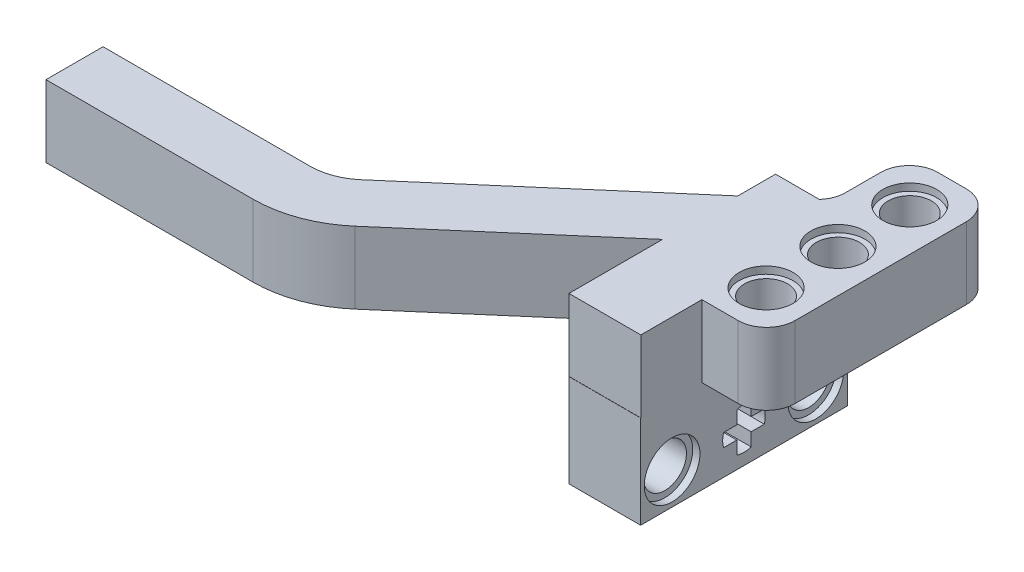
SolidWorks part; units mm, degrees
ref_plane "Front Plane" through (0, 0, 0) normal (0, 0, 1) x (1, 0, 0)
ref_plane "Top Plane" through (0, 0, 0) normal (0, 1, 0) x (1, 0, 0)
ref_plane "Right Plane" through (0, 0, 0) normal (1, 0, 0) x (0, 0, -1)
sketch "Sketch6" plane through (0, 0, 0) normal (0, 1, 0) x (1, 0, 0)
  line L1 (-4.7625, 12.7) -> (4.7625, 12.7)
  line L2 (-4.7625, 12.7) -> (-4.7625, -12.7)
  line L3 (-4.7625, -12.7) -> (4.7625, -12.7)
  line L4 (4.7625, 12.7) -> (4.7625, -12.7)
  line L5 (-4.7625, 12.7) -> (4.7625, -12.7) construction
  line L6 (-4.7625, -12.7) -> (4.7625, 12.7) construction
  point P0 (0, 0)
  dimension "D1" = 9.525
  dimension "D2" = 25.4
extrude "Boss-Extrude1" add sketch "Sketch6" against normal blind 8
sketch "Sketch16" plane through (0, 0, 0) normal (0, -1, 0) x (1, 0, 0)
  line L1 (-2.4423, -3.5) -> (-10.4423, -3.5)
  line L2 (-2.4423, -3.5) -> (-2.4423, 19.5)
  line L3 (-2.4423, 19.5) -> (-10.4423, 19.5)
  line L4 (-10.4423, -3.5) -> (-10.4423, 19.5)
  line L5 (-2.4423, -3.5) -> (-10.4423, 19.5) construction
  line L6 (-2.4423, 19.5) -> (-10.4423, -3.5) construction
  line L7 (-4.7625, -12.7) -> (-4.7625, 12.7) construction
  point P0 (-6.4423, 8)
  point P5 (6.4422, 5.5566)
  point P7 (-6.5033, 8.0602)
  point P10 (3.2311, 3.8232)
  point P12 (-4.7625, 0)
  dimension "D1" = 6.4423
  dimension "D2" = 8
  dimension "D3" = 8
  dimension "D4" = 23
extrude "Boss-Extrude6" add sketch "Sketch16" along normal up to surface (8 mm away) up to face at (0, -8, 0)
sketch "Sketch7" plane through (0, 0, 0) normal (0, 1, 0) x (1, 0, 0)
  circle A0 centre (0, 8) radius 2.4
  circle A1 centre (0, 0) radius 2.4
  circle A2 centre (0, -8) radius 2.4
  circle A3 centre (0, 8) radius 3
  circle A4 centre (0, 0) radius 3
  circle A5 centre (0, -8) radius 3
  dimension "D3" = 4.8
  dimension "D1" = 8
  dimension "D2" = 8
  dimension "D4" = 0.6
extrude "Cut-Extrude1" cut sketch "Sketch7" against normal blind 0.8
extrude "Cut-Extrude2" cut sketch "Sketch7<3>" against normal blind 7.2 contours A0 | A1 | A2 region at (0, 0, -8) region at (0, 0, 0) region at (0, 0, 8)
sketch "Sketch7<3>" plane through (0, 0, 0) normal (0, 1, 0) x (1, 0, 0) same geometry as "Sketch7"
sketch "Sketch9" plane through (0, -7.2, -7.2) normal (0, 1, 0) x (1, 0, 0)
  circle A0 centre (0, 0.8) radius 2.4
  circle A1 centre (0, -7.2) radius 2.4
  circle A2 centre (0, -15.2) radius 2.4
  circle A3 centre (0, 0.8) radius 3
  circle A4 centre (0, -7.2) radius 3
  circle A5 centre (0, -15.2) radius 3
  dimension "D3" = 4.8
  dimension "D1" = 8
  dimension "D2" = 8
  dimension "D4" = 0.6
extrude "Cut-Extrude4" cut sketch "Sketch9" against normal blind 0.8 contours A3 | A4 | A5
ref_plane "Plane4" through (0, 0, 28) normal (0, 0, 1) x (1, 0, 0)
sketch "Sketch10" plane through (0, -8, 0) normal (0, -1, 0) x (-1, 0, 0)
  line L1 (4.7625, 4.1904) -> (34.7625, -21.65)
  line L2 (4.7625, 4.1904) -> (4.7625, -4.1904) construction
  line L3 (34.7625, -21.65) -> (60.1625, -21.65)
  line L4 (60.1625, -21.65) -> (60.1625, -28)
  line L5 (-57.9984, -28) -> (57.9984, -28) construction
  line L8 (4.7625, -4.1904) -> (32.4047, -28)
  line L10 (4.7625, 4.1904) -> (4.7625, -4.1904)
  line L14 (4.7625, 12.7) -> (4.7625, 3.5) construction
  line L18 (32.4047, -28) -> (60.1625, -28)
  point P2 (4.7625, 0)
  dimension "D1" = 30
  dimension "D2" = 6.35
  dimension "D3" = 25.4
  dimension "D4" = 6.35
extrude "Boss-Extrude3" add sketch "Sketch10" against normal up to surface (8 mm away) up to face at (0, 0, -5)
fillet "Fillet1" radius 3.175 1 edges at (-4.7625, -4, -4.1904)
fillet "Fillet3" radius 3.175 3 edges at (4.7625, -4, -12.7) (4.7625, -4, 12.7) (-4.7625, -4, -12.7)
fillet "Fillet6" radius 12.7 1 edges at (-32.4047, -4, 28)
fillet "Fillet7" radius 6.35 1 edges at (-34.7625, -4, 21.65)
sketch "Sketch11" plane through (0, -8, 0) normal (0, -1, 0) x (-1, 0, 0)
  line L0 (4.7625, 9.525) -> (4.7625, 5.6089) construction
  line L1 (10.4422, -19.5186) -> (2.4422, -19.5186)
  line L2 (10.4422, -19.5186) -> (10.4422, 3.4814)
  line L3 (10.4422, 3.4814) -> (2.4422, 3.4814)
  line L4 (2.4422, -19.5186) -> (2.4422, 3.4814)
  line L5 (10.4422, -19.5186) -> (2.4422, 3.4814) construction
  line L6 (10.4422, 3.4814) -> (2.4422, -19.5186) construction
  point P0 (6.4422, -8.0186)
  point P5 (6.4422, 5.5566)
  point P9 (4.7625, 7.5669)
  point P10 (3.2311, 3.8232)
  dimension "D1" = 6.4422
  dimension "D2" = 15.5855
  dimension "D3" = 8
  dimension "D4" = 23
extrude "Boss-Extrude4" add sketch "Sketch11" along normal blind 6.7462 contours L4 L3 L2 L1
sketch "Sketch13" plane through (-2.4423, 0, 0) normal (1, 0, 0) x (0, 0, -1)
  line L0 (-19.5186, -14.7462) -> (3.4814, -14.7462) construction
  line L1 (-8.8186, -14.0148) -> (-8.8186, -12.5521)
  line L2 (-7.2186, -12.5521) -> (-7.2186, -14.0148)
  line L3 (-8.8186, -14.0148) -> (-7.2186, -14.0148) construction
  line L4 (-8.8186, -14.0148) -> (-8.8186, -15.4775) construction
  line L5 (-8.8186, -14.0148) -> (-10.2813, -14.0148)
  line L6 (-10.2813, -15.4775) -> (-8.8186, -15.4775)
  line L7 (-8.8186, -15.4775) -> (-8.8186, -16.9403)
  line L8 (-7.2186, -16.9403) -> (-7.2186, -15.4775)
  line L9 (-7.2186, -15.4775) -> (-5.7558, -15.4775)
  line L10 (-7.2186, -14.0148) -> (-5.7558, -14.0148)
  line L11 (-5.7558, -14.0148) -> (-5.9183, -14.0148)
  circle A0 centre (-8.0186, -14.7462) radius 2.5157 construction
  circle A1 centre (-16.0186, -14.7462) radius 3.1
  circle A2 centre (-0.0186, -14.7462) radius 3.1
  circle A3 centre (-16.0186, -14.7462) radius 2.4
  circle A4 centre (-0.0186, -14.7462) radius 2.4
  arc A5 (-8.8186, -12.5521) -> (-7.2186, -12.5521) centre (-8.0186, -15.0259) cw
  arc A6 (-10.2813, -14.0148) -> (-10.2813, -15.4775) centre (-7.7863, -14.7462) ccw
  arc A7 (-8.8186, -16.9403) -> (-7.2186, -16.9403) centre (-8.0186, -14.4664) ccw
  arc A8 (-5.7558, -14.0148) -> (-5.7558, -15.4775) centre (-8.2509, -14.7462) cw
  point P14 (-8.0186, -14.0148)
  point P16 (-8.8186, -14.7462)
  point P17 (0, 0)
  line M4 (-19.5186, -14.7462) -> (3.4814, -14.7462)
  dimension "D1" = 6.2
  dimension "D2" = 4.8
  dimension "D7" = 2.6
  dimension "D3" = 8
  dimension "D4" = 8
  dimension "D5" = 1.4627
  dimension "D6" = 1.6
sketch "Sketch14" plane through (0, -14.7462, 0) normal (0, -1, 0) x (-1, 0, 0)
  line L1 (10.4422, -19.5186) -> (2.4422, -19.5186)
  line L2 (10.4422, -19.5186) -> (10.4422, 3.4814)
  line L3 (10.4422, 3.4814) -> (2.4422, 3.4814)
  line L4 (2.4422, -19.5186) -> (2.4422, 3.4814)
extrude "Boss-Extrude5" add sketch "Sketch14" along normal blind 3.6 contours L2 L3 L4 L1
extrude "Cut-Extrude5" cut sketch "Sketch13" against normal blind 0.8 contours A3 A1 M4 | A3 A1 M4 | A8 A6 L6 L7 A7 L8 L9 M4 | A8 L10 L2 A5 L1 L5 A6 M4 | A4 A2 M4 | A4 A2 M4 region at (-2.4423, -11.7155, 0.0186) region at (-2.4423, -14.8155, 2.7686) region at (-2.4423, -17.7768, 16.0186) region at (-2.4423, -14.6768, 13.2686) region at (-2.4423, -13.9029, 8.0186) region at (-2.4423, -15.5895, 8.0186)
extrude "Cut-Extrude6" cut sketch "Sketch13<3>" against normal through all contours A8 A6 L6 L7 A7 L8 L9 M4 | A8 L10 L2 A5 L1 L5 A6 M4 | A4 M4 | A4 M4 | A3 region at (-2.4423, -13.9029, 8.0186) region at (-2.4423, -15.5895, 8.0186) region at (-2.4423, -15.7648, 0.0186) region at (-2.4423, -13.7276, 0.0186)
sketch "Sketch13<3>" plane through (-2.4423, 0, 0) normal (1, 0, 0) x (0, 0, -1) same geometry as "Sketch13"
ref_plane "Plane5" through (-6.4423, 0, 0) normal (1, 0, 0) x (0, 0, -1)
mirror "Mirror1" about plane through (-6.4423, 0, 0) normal (1, 0, 0) of "Cut-Extrude5"
